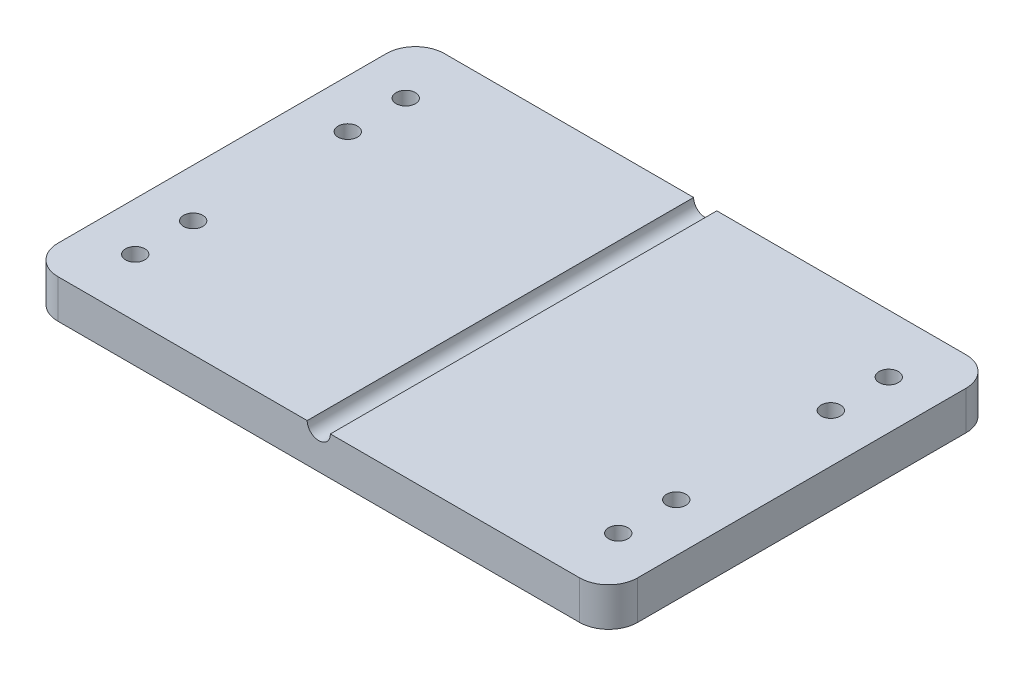
SolidWorks part; units mm, degrees
ref_plane "Front Plane" through (0, 0, 0) normal (0, 0, 1) x (1, 0, 0)
ref_plane "Top Plane" through (0, 0, 0) normal (0, 1, 0) x (1, 0, 0)
ref_plane "Right Plane" through (0, 0, 0) normal (1, 0, 0) x (0, 0, -1)
sketch "Sketch1" plane through (0, 0, 0) normal (0, 1, 0) x (1, 0, 0)
  circle A0 centre (0, 0) radius 5
  dimension "D1" = 10
extrude "Boss-Extrude1" add sketch "Sketch1" along normal blind 0.2
sketch "Sketch2" plane through (0, 0.2, 0) normal (0, 1, 0) x (1, 0, 0)
  line L1 (-15, 10) -> (15, 10)
  line L2 (-15, 10) -> (-15, -10)
  line L3 (-15, -10) -> (15, -10)
  line L4 (15, 10) -> (15, -10)
  line L5 (-15, 10) -> (15, -10) construction
  line L6 (-15, -10) -> (15, 10) construction
  point P0 (0, 0)
  dimension "D1" = 20
  dimension "D2" = 30
extrude "Boss-Extrude2" add sketch "Sketch2" along normal blind 2
fillet "Fillet1" radius 1.5 4 edges at (15, 1.2, 10) (15, 1.2, -10) (-15, 1.2, -10) (-15, 1.2, 10)
sketch "Sketch3" plane through (0, 0, 10) normal (0, 0, 1) x (1, 0, 0)
  line L0 (-13.5, 2.2) -> (13.5, 2.2) construction
  circle A0 centre (0, 2.2) radius 0.6
  dimension "D1" = 1.2
extrude "Cut-Extrude1" cut sketch "Sketch3" against normal through all
sketch "Sketch4" plane through (0, 0, 0) normal (0, -1, 0) x (-1, 0, 0)
  circle A0 centre (0, 0) radius 5
  dimension "D1" = 10
extrude "Cut-Extrude2" cut sketch "Sketch4" against normal up to surface (0.2 mm away) up to face at (0, 0.2, 5)
sketch "Sketch5" plane through (0, 0.2, 0) normal (0, -1, 0) x (-1, 0, 0)
  circle A0 centre (0, 0) radius 5
  circle A1 centre (0, 0) radius 5.5
  dimension "D1" = 10
  dimension "D2" = 11
extrude "Cut-Extrude3" cut sketch "Sketch5" against normal blind 0.2
sketch "Sketch6" plane through (0, 2.2, 0) normal (0, 1, 0) x (1, 0, 0)
  line L0 (12.5, -10) -> (12.5, 10) construction
  line L1 (0.6, -10) -> (13.5, -10) construction
  line L2 (13.5, 10) -> (0.6, 10) construction
  line L3 (15, -8.5) -> (15, 8.5) construction
  circle A0 centre (12.5, -7) radius 0.5
  circle A1 centre (12.5, -4) radius 0.5
  circle A2 centre (12.5, 7) radius 0.5
  circle A3 centre (12.5, 4) radius 0.5
  dimension "D1" = 1
  dimension "D2" = 1
  dimension "D3" = 1
  dimension "D4" = 1
  dimension "D8" = 3
  dimension "D5" = 3
  dimension "D6" = 3
  dimension "D7" = 3
  dimension "D9" = 2.5
extrude "Cut-Extrude4" cut sketch "Sketch6" against normal through all
mirror "Mirror1" about plane through (0, 0, 0) normal (1, 0, 0) of "Cut-Extrude4"
